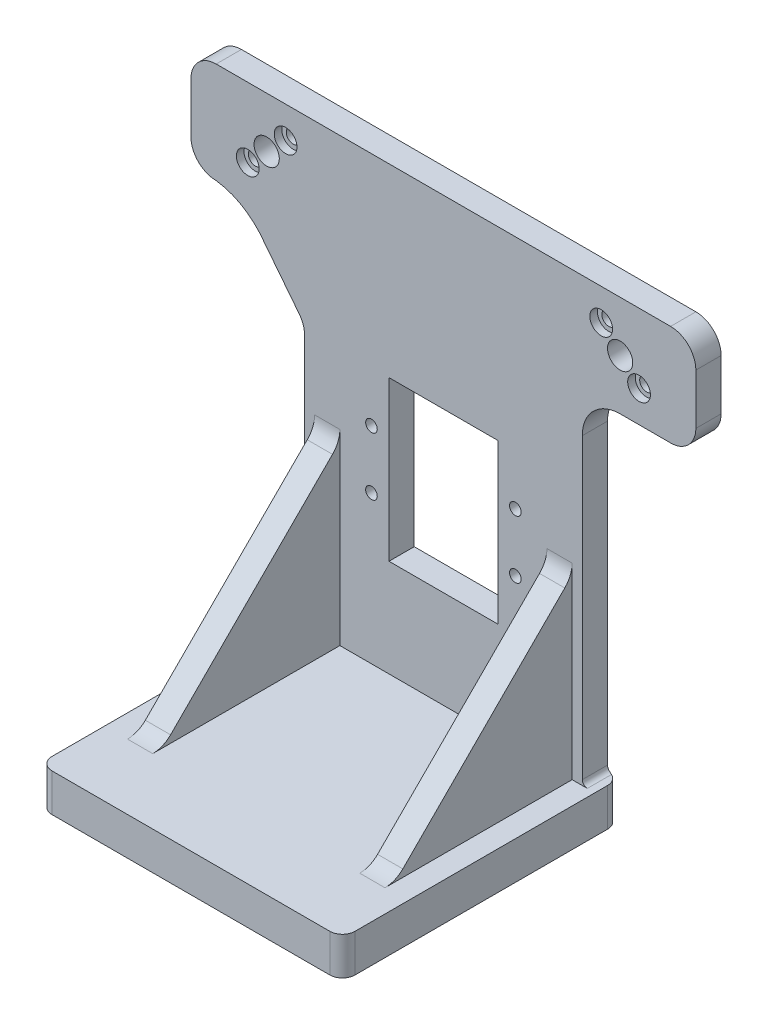
SolidWorks part; units mm, degrees
ref_plane "Ebene vorne" through (0, 0, 0) normal (0, 0, 1) x (1, 0, 0)
ref_plane "Ebene oben" through (0, 0, 0) normal (0, 1, 0) x (1, 0, 0)
ref_plane "Ebene rechts" through (0, 0, 0) normal (1, 0, 0) x (0, 0, -1)
sketch "Skizze1" plane through (0, 0, 0) normal (0, 0, 1) x (1, 0, 0)
  line L0 (0, 0) -> (0, 120.8446) construction
  line L1 (0, 120.8446) -> (0, -115.4537) construction
  line L2 (-21.55, 2.2046) -> (-75.2531, 2.2046) construction
  line L15 (90, 107.0546) -> (-90, 107.0546)
  line L16 (-100, 97.0546) -> (-100, 77.0546)
  line L17 (-90, 67.0546) -> (-70, 67.0546)
  line L18 (-55, 52.0546) -> (-55, -67.9454)
  line L19 (-55, -67.9454) -> (-60, -67.9454)
  line L20 (-60, -67.9454) -> (-60, -82.9454)
  line L21 (-60, -82.9454) -> (60, -82.9454)
  line L22 (60, -67.9454) -> (60, -82.9454)
  line L23 (55, -67.9454) -> (60, -67.9454)
  line L24 (55, 52.0546) -> (55, -67.9454)
  line L25 (90, 67.0546) -> (70, 67.0546)
  line L26 (100, 97.0546) -> (100, 77.0546)
  line L27 (21.55, 33.7046) -> (-21.55, 33.7046)
  line L28 (-21.55, 33.7046) -> (-21.55, -29.2954)
  line L29 (-21.55, -29.2954) -> (21.55, -29.2954)
  line L30 (-28.5, 26.717) -> (-28.5, -23.7709) construction
  line L31 (21.55, 33.7046) -> (21.55, -29.2954)
  line L32 (-152.8572, 87.0546) -> (12.8572, 87.0546) construction
  line L33 (-62.5, 94.5546) -> (-83.4096, 94.5546) construction
  line L34 (-77.5, 79.5546) -> (-83.4096, 79.5546) construction
  line L35 (-62.5, 94.5546) -> (-62.5, 69.0538) construction
  line L36 (-77.5, 79.5546) -> (-77.5, 100.8525) construction
  line L37 (-21.55, 2.2046) -> (21.55, 2.2046) construction
  line L38 (-55, -67.9454) -> (55, -67.9454) construction
  arc A0 (-100, 77.0546) -> (-90, 67.0546) centre (-90, 77.0546) ccw
  arc A1 (-90, 107.0546) -> (-100, 97.0546) centre (-90, 97.0546) ccw
  arc A2 (-70, 67.0546) -> (-55, 52.0546) centre (-70, 52.0546) cw
  arc A3 (70, 67.0546) -> (55, 52.0546) centre (70, 52.0546) ccw
  arc A4 (90, 107.0546) -> (100, 97.0546) centre (90, 97.0546) cw
  arc A5 (100, 77.0546) -> (90, 67.0546) centre (90, 77.0546) cw
  circle A6 centre (-28.5, 13.7046) radius 2.3
  circle A7 centre (-28.5, -9.2954) radius 2.3
  circle A8 centre (28.5, -9.2954) radius 2.3
  circle A9 centre (28.5, 13.7046) radius 2.3
  circle A10 centre (-70, 87.0546) radius 5
  circle A11 centre (-62.5, 94.5546) radius 2.75
  circle A12 centre (-77.5, 79.5546) radius 2.75
  circle A13 centre (77.5, 79.5546) radius 2.75
  circle A14 centre (62.5, 94.5546) radius 2.75
  circle A15 centre (70, 87.0546) radius 5
  point P18 (-100, 107.0546)
  point P22 (0, 107.0546)
  point P23 (0, -82.9454)
  point P33 (100, 107.0546)
  point P50 (0, -29.2954)
  point P51 (0, 33.7046)
  dimension "D7" = 10
  dimension "D8" = 15
  dimension "D11" = 4.6
  dimension "D12" = 4.6
  dimension "D15" = 10
  dimension "D16" = 5.5
  dimension "D17" = 5.5
  dimension "D1" = 100
  dimension "D2" = 55
  dimension "D3" = 60
  dimension "D4" = 40
  dimension "D5" = 135
  dimension "D6" = 15
  dimension "D9" = 63
  dimension "D10" = 21.55
  dimension "D13" = 28.5
  dimension "D14" = 23
  dimension "D18" = 7.5
  dimension "D19" = 7.5
  dimension "D20" = 7.5
  dimension "D21" = 7.5
  dimension "D22" = 20
  dimension "D23" = 140
  dimension "D24" = 84.85
extrude "Aufsatz-Linear austragen1" add sketch "Skizze1" along normal blind 10
sketch "Skizze2" plane through (0, 0, 10) normal (0, 0, 1) x (1, 0, 0)
  line L0 (-21.55, 2.2046) -> (21.55, 2.2046) construction
  line L1 (-21.55, 33.7046) -> (-21.55, -29.2954) construction
  line L2 (21.55, -29.2954) -> (21.55, 33.7046) construction
  line L3 (0, 33.7046) -> (0, -29.2954) construction
  line L4 (21.55, 33.7046) -> (-21.55, 33.7046) construction
  line L5 (-21.55, -29.2954) -> (21.55, -29.2954) construction
  line L6 (-70, 92.0546) -> (-70, 82.0546) construction
  line L7 (-65, 87.0546) -> (-75, 87.0546) construction
  line L8 (-13.4991, -8.9319) -> (-83.4991, 75.9181)
  line L9 (-56.5009, 98.1912) -> (13.4991, 13.3412)
  circle A0 centre (-70, 87.0546) radius 5 construction
  circle A1 centre (0, 2.2046) radius 17.5
  circle A2 centre (-70, 87.0546) radius 17.5
  dimension "D1" = 35
  dimension "D2" = 35
sketch "Skizze3" plane through (0, 0, 10) normal (0, 0, 1) x (1, 0, 0)
  line L0 (-90, 67.0546) -> (-70, 67.0546) construction
  line L1 (-72.8459, 57.8146) -> (-56.7743, 37.3523)
  line L2 (-55, 52.0546) -> (-55, -67.9454) construction
  line L3 (-55, 18.961) -> (-43.3334, 21.2005)
  line L4 (-43.3334, 21.2005) -> (-45.498, 67.0546)
  line L5 (-45.498, 67.0546) -> (-90, 67.0546)
  arc A0 (-100, 77.0546) -> (-90, 67.0546) centre (-90, 77.0546) ccw construction
  spline S0 degree 2 poles (-90, 67.0546) (-79.9383, 65.6564) (-72.8459, 57.8146) knots 0 0 0 1 1 1
  spline S1 degree 2 poles (-55, 18.961) (-46.6365, 27.9631) (-56.7743, 37.3523) knots 0 0 0 1 1 1
extrude "Aufsatz-Linear austragen3" add sketch "Skizze3" against normal blind 10
sketch "Skizze4" plane through (0, 0, 10) normal (0, 0, 1) x (1, 0, 0)
  line L1 (-60, -67.9454) -> (60, -67.9454)
  line L2 (-60, -67.9454) -> (-60, -82.9454)
  line L3 (-60, -82.9454) -> (60, -82.9454)
  line L4 (60, -67.9454) -> (60, -82.9454)
extrude "Aufsatz-Linear austragen4" add sketch "Skizze4" along normal blind 100
sketch "Skizze6" plane through (-55, 0, 0) normal (-1, 0, 0) x (0, 0, 1)
  line L5 (60.1366, -67.0551) -> (60.1366, -66.9447)
ref_plane "Ebene1" through (-51, 0, 0) normal (-1, 0, 0) x (0, 0, 1)
sketch "Skizze9" plane through (-51, 0, 0) normal (-1, 0, 0) x (0, 0, 1)
  line L0 (10, 2.0546) -> (80, -67.9454)
  line L1 (10, 35.555) -> (10, -67.9454) construction
  line L2 (110, -67.9454) -> (0, -67.9454) construction
  line L3 (80, -67.9454) -> (6.6442, -67.9454)
  line L4 (10, -67.9454) -> (0, -67.9454) construction
  line L5 (6.6442, -67.9454) -> (6.6442, 2.0546)
  line L6 (6.6442, 2.0546) -> (10, 2.0546)
  dimension "D1" = 70
  dimension "D2" = 70
extrude "Aufsatz-Linear austragen5" add sketch "Skizze9" against normal blind 10
ref_plane "Ebene2" through (51, 0, 0) normal (1, 0, 0) x (0, 0, -1)
sketch "Skizze10" plane through (51, 0, 0) normal (1, 0, 0) x (0, 0, -1)
  line L0 (-10, 2.2046) -> (-80, -67.9454)
  line L1 (-10, 19.7046) -> (-10, -15.2954) construction
  line L2 (-80, -67.9454) -> (-10, -67.9454)
  line L3 (-110, -67.9454) -> (0, -67.9454) construction
  line L4 (-80, -67.9454) -> (-10, -67.9454) construction
  line L5 (-10, -67.9454) -> (-10, 2.2046)
extrude "Aufsatz-Linear austragen6" add sketch "Skizze10" against normal blind 10
fillet "Verrundung3" radius 10 4 edges at (-46, -67.9454, 80) (46, -67.9454, 80) (46, 2.2046, 10) (-46, 2.0546, 10)
fillet "Verrundung4" radius 5 4 edges at (-60, -75.4454, 110) (60, -75.4454, 110) (60, -75.4454, 0) (-60, -75.4454, 0)
fillet "Verrundung5" radius 10 1 edges at (-55, 35.555, 5)
sketch "Skizze11" plane through (0, 0, 10) normal (0, 0, 1) x (1, 0, 0)
  circle A0 centre (62.5, 94.5546) radius 4.5
  circle A2 centre (77.5, 79.5546) radius 4.5
  circle A3 centre (-62.5, 94.5546) radius 4.5
  circle A4 centre (-77.5, 79.5546) radius 4.5
  dimension "D1" = 9
  dimension "D2" = 9
  dimension "D3" = 9
  dimension "D4" = 9
extrude "Schnitt-Linear austragen1" cut sketch "Skizze11" against normal blind 3
sketch "Skizze12" plane through (0, 0, 0) normal (0, 0, -1) x (-1, 0, 0)
  line L0 (26.2, 13.7046) -> (30.8, 13.7046) construction
  line L1 (28.5, 16.0046) -> (28.5, 11.4046) construction
  line L2 (28.5, 16.0046) -> (28.5, 17.7471) construction
  line L3 (28.5, 11.4046) -> (28.5, 9.6621) construction
  line L4 (28.5, 17.7471) -> (24.825, 15.7871)
  line L5 (24.825, 15.7871) -> (24.825, 11.6221)
  line L6 (24.825, 11.6221) -> (28.5, 9.6621)
  line L7 (32.175, 11.6221) -> (28.5, 9.6621)
  line L8 (32.175, 15.7871) -> (32.175, 11.6221)
  line L9 (28.5, 17.7471) -> (32.175, 15.7871)
  line L10 (26.2, -9.2954) -> (30.8, -9.2954) construction
  line L11 (28.5, -6.9954) -> (28.5, -11.5954) construction
  line L12 (28.5, -6.9954) -> (28.5, -5.2529) construction
  line L13 (28.5, -11.5954) -> (28.5, -13.3379) construction
  line L14 (28.5, -5.2529) -> (24.825, -7.2129)
  line L15 (24.825, -7.2129) -> (24.825, -11.3779)
  line L16 (24.825, -11.3779) -> (28.5, -13.3379)
  line L17 (32.175, -11.3779) -> (28.5, -13.3379)
  line L18 (32.175, -7.2129) -> (32.175, -11.3779)
  line L19 (28.5, -5.2529) -> (32.175, -7.2129)
  line L20 (-30.8, -9.2954) -> (-26.2, -9.2954) construction
  line L21 (-28.5, -6.9954) -> (-28.5, -11.5954) construction
  line L22 (-28.5, -6.9954) -> (-28.5, -5.2529) construction
  line L23 (-28.5, -11.5954) -> (-28.5, -13.3379) construction
  line L24 (-28.5, -5.2529) -> (-32.175, -7.2129)
  line L25 (-32.175, -7.2129) -> (-32.175, -11.3779)
  line L26 (-32.175, -11.3779) -> (-28.5, -13.3379)
  line L27 (-24.825, -11.3779) -> (-28.5, -13.3379)
  line L28 (-24.825, -7.2129) -> (-24.825, -11.3779)
  line L29 (-28.5, -5.2529) -> (-24.825, -7.2129)
  line L30 (-30.8, 13.7046) -> (-26.2, 13.7046) construction
  line L31 (-28.5, 16.0046) -> (-28.5, 11.4046) construction
  line L32 (-28.5, 16.0046) -> (-28.5, 17.7471) construction
  line L33 (-28.5, 11.4046) -> (-28.5, 9.6621) construction
  line L34 (-28.5, 17.7471) -> (-32.175, 15.7871)
  line L35 (-32.175, 15.7871) -> (-32.175, 11.6221)
  line L36 (-32.175, 11.6221) -> (-28.5, 9.6621)
  line L37 (-24.825, 11.6221) -> (-28.5, 9.6621)
  line L38 (-24.825, 15.7871) -> (-24.825, 11.6221)
  line L39 (-28.5, 17.7471) -> (-24.825, 15.7871)
  circle A0 centre (28.5, 13.7046) radius 2.3 construction
  circle A1 centre (28.5, -9.2954) radius 2.3 construction
  circle A2 centre (-28.5, -9.2954) radius 2.3 construction
  circle A3 centre (-28.5, 13.7046) radius 2.3 construction
  dimension "D1" = 8.085
  dimension "D2" = 3.675
  dimension "D3" = 8.085
  dimension "D4" = 3.675
  dimension "D5" = 8.085
  dimension "D6" = 3.675
  dimension "D7" = 8.085
  dimension "D8" = 3.675
extrude "Schnitt-Linear austragen2" cut sketch "Skizze12" against normal blind 3
fillet "Verrundung6" radius 2 2 edges at (55, -67.9454, 5) (-55, -67.9454, 5)
equation "\"D10@Skizze1\"=43.1/2"
equation "\"D13@Skizze1\"=57/2"
